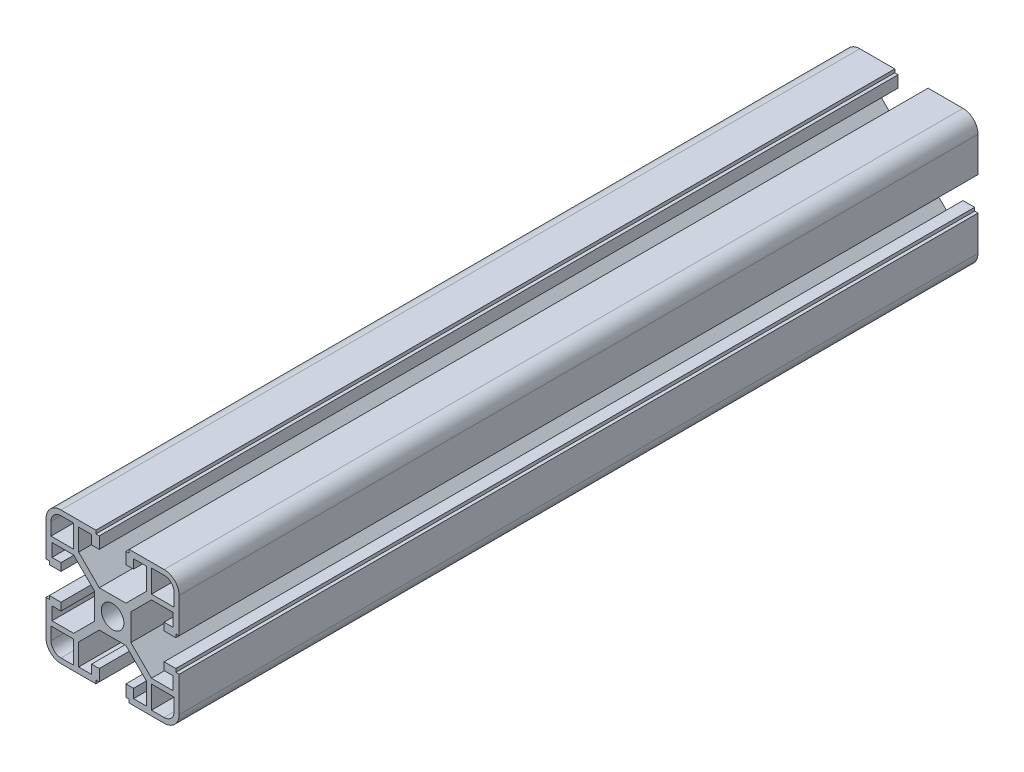
SolidWorks part; units mm, degrees
material "6061-T6 (SS)"
ref_plane "Front Plane" through (0, 0, 0) normal (0, 0, 1) x (1, 0, 0)
ref_plane "Top Plane" through (0, 0, 0) normal (0, 1, 0) x (1, 0, 0)
ref_plane "Right Plane" through (0, 0, 0) normal (1, 0, 0) x (0, 0, -1)
sketch "Sketch1" plane through (0, 0, 0) normal (0, 0, 1) x (1, 0, 0)
  line L0 (3.4, 0) -> (5.5, 0)
  line L1 (10.19, 11.69) -> (4, 5.5)
  line L2 (11.69, 10.19) -> (5.5, 4)
  line L3 (18.2, 10.19) -> (11.69, 10.19)
  line L4 (18.2, 10.19) -> (18.2, 6.3)
  line L5 (18.2, 6.3) -> (15.5, 6.3)
  line L6 (15.5, 6.3) -> (15.5, 4)
  line L7 (15.5, 4) -> (19, 4)
  line L8 (19, 4) -> (19, 5)
  line L9 (19, 5) -> (20, 5)
  line L10 (20, 5) -> (20, 15.5)
  line L11 (15.5, 20) -> (5, 20)
  line L12 (18.5, 11.69) -> (18.5, 15.5)
  line L13 (15.5, 18.5) -> (11.69, 18.5)
  line L14 (11.69, 11.69) -> (11.69, 18.5)
  line L15 (0, 3.4) -> (0, 5.5)
  line L16 (4, 5.5) -> (0, 5.5)
  line L17 (5, 20) -> (5, 19)
  line L18 (5.5, 0) -> (5.5, 4)
  line L19 (5, 19) -> (4, 19)
  line L20 (4, 19) -> (4, 15.5)
  line L21 (4, 15.5) -> (6.3, 15.5)
  line L22 (10.19, 11.69) -> (10.19, 18.2)
  line L23 (11.69, 11.69) -> (18.5, 11.69)
  line L24 (6.3, 18.2) -> (6.3, 15.5)
  line L25 (10.19, 18.2) -> (6.3, 18.2)
  arc A0 (20, 15.5) -> (15.5, 20) centre (15.5, 15.5) ccw
  arc A1 (18.5, 15.5) -> (15.5, 18.5) centre (15.5, 15.5) ccw
  arc A2 (3.4, 0) -> (0, 3.4) centre (0, 0) ccw
  point P4 (0, 4.45)
  dimension "D3" = 4.5
  dimension "D18" = 1.5
  dimension "D9" = 3.4
  dimension "D20" = 1.8
  dimension "D25" = 3
  dimension "D1" = 5.5
  dimension "D2" = 1.5
  dimension "D4" = 14.5
  dimension "D5" = 1.5
  dimension "D6" = 2.1
  dimension "D7" = 2.3
  dimension "D8" = 1.8
  dimension "D10" = 6.81
  dimension "D11" = 2.1
  dimension "D12" = 1
  dimension "D13" = 4.5
  dimension "D14" = 45
  dimension "D15" = 14.5
  dimension "D16" = 1
  dimension "D17" = 1.5
  dimension "D19" = 6.81
  dimension "D21" = 4.5
  dimension "D22" = 2.3
  dimension "D23" = 1
  dimension "D24" = 1
  dimension "D26" = 8.754
  dimension "D27" = 8.754
  dimension "D28" = 4
  dimension "D29" = 4
extrude "Boss-Extrude1" add sketch "Sketch1" along normal blind 240
mirror "Mirror1" about plane through (0, 0, 0) normal (0, 1, 0) of "Boss-Extrude1"
mirror "Mirror2" about plane through (0, 0, 0) normal (1, 0, 0) of "Boss-Extrude1"
mirror "Mirror3" about plane through (0, 0, 0) normal (0, 1, 0) of "Mirror2"
